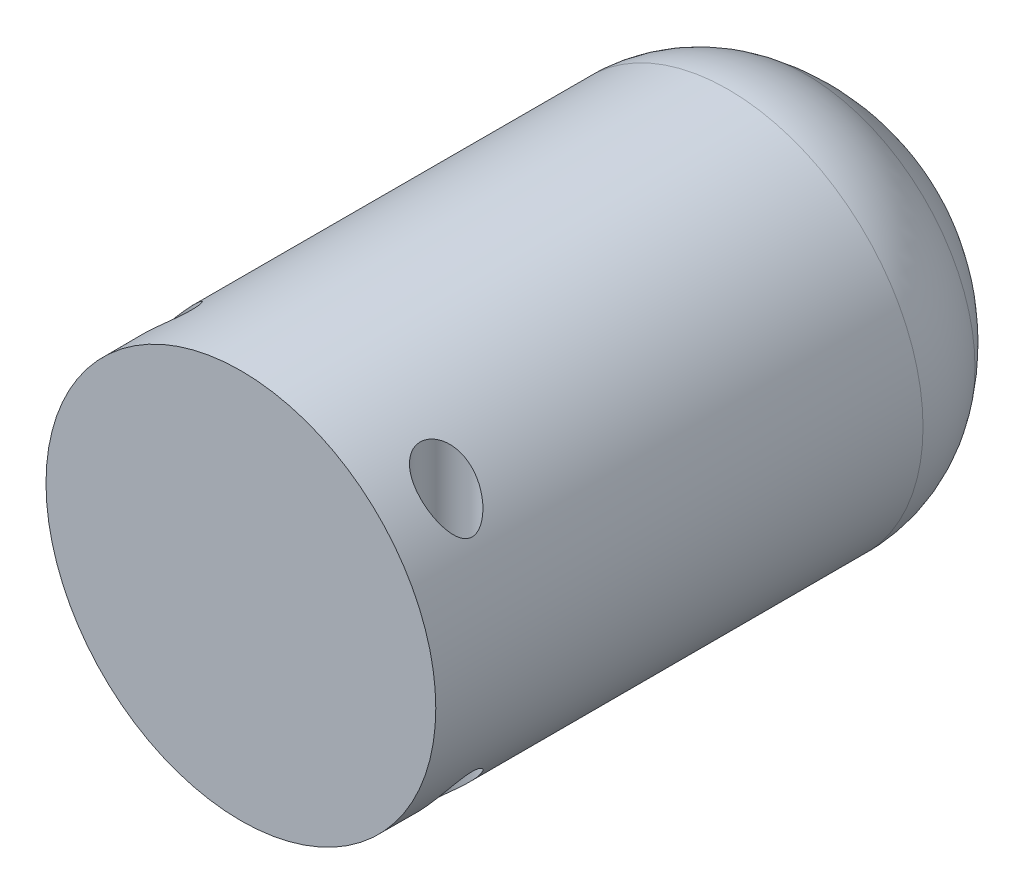
SolidWorks part; units mm, degrees
ref_plane "Front Plane" through (0, 0, 0) normal (0, 0, 1) x (1, 0, 0)
ref_plane "Top Plane" through (0, 0, 0) normal (0, 1, 0) x (1, 0, 0)
ref_plane "Right Plane" through (0, 0, 0) normal (1, 0, 0) x (0, 0, -1)
sketch "Sketch1" plane through (0, 0, 0) normal (0, 0, 1) x (1, 0, 0)
  circle A0 centre (0, 0) radius 1.5
  dimension "D1" = 3
extrude "Boss-Extrude1" add sketch "Sketch1" along normal blind 4
dome "Dome1" faces to dome 1 distance 1 reverse direction no elliptical dome no face at (1.5, 0, 0) parameters "D1"=1
fillet "Fillet1" radius 1 1 edges at (1.5, 0, 0)
sketch "Sketch3" plane through (0, 0, 0) normal (0, 1, 0) x (1, 0, 0)
  line L0 (0, 0) -> (0, -2.3502) construction
  circle A0 centre (1.08, -3.5) radius 0.2
  circle A1 centre (-1.08, -3.5) radius 0.2
  point P7 (0.2064, -1.6364)
  dimension "D3" = 0.4
  dimension "D1" = 2.16
  dimension "D2" = 3.5
extrude "Cut-Extrude1" cut sketch "Sketch3" against normal through all both and the other way through all
